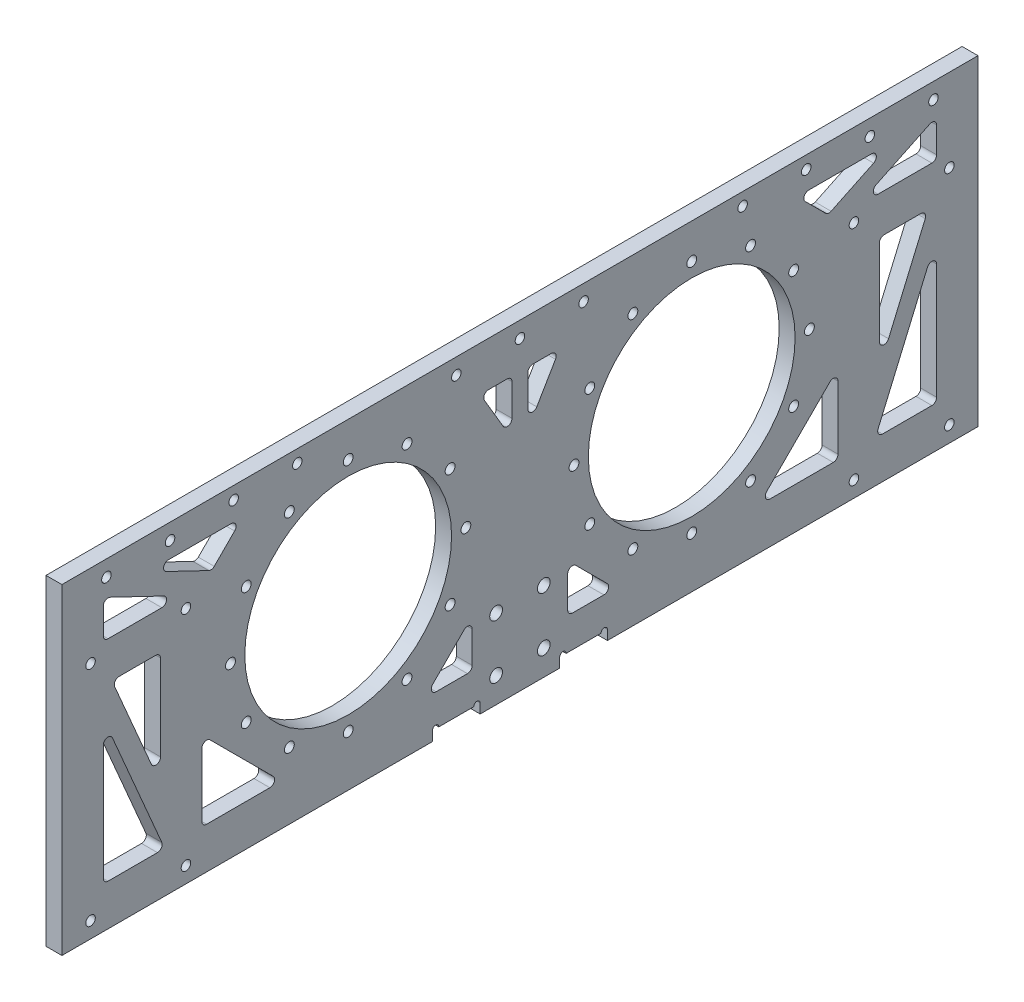
SolidWorks part; units mm, degrees
material "Thornel Mat VMA"
ref_plane "前视基准面" through (0, 0, 0) normal (0, 0, 1) x (1, 0, 0)
ref_plane "上视基准面" through (0, 0, 0) normal (0, 1, 0) x (1, 0, 0)
ref_plane "右视基准面" through (0, 0, 0) normal (1, 0, 0) x (0, 0, -1)
sketch "草图1" plane through (0, 0, 0) normal (1, 0, 0) x (0, 0, -1)
  line L0 (54, 48) -> (54, -53) construction
  line L1 (-90, -53) -> (198, -53)
  line L2 (-90, -53) -> (-90, 48)
  line L3 (-90, 48) -> (198, 48)
  line L4 (198, -53) -> (198, 48)
  line L5 (-36, 44) -> (-16, 44) construction
  line L6 (46.5, -45) -> (61.5, -45) construction
  line L7 (46.5, -45) -> (46.5, -28) construction
  line L8 (46.5, -28) -> (61.5, -28) construction
  line L9 (61.5, -45) -> (61.5, -28) construction
  line L10 (46.5, -45) -> (61.5, -28) construction
  line L11 (46.5, -28) -> (61.5, -45) construction
  line L12 (144, 44) -> (124, 44) construction
  circle A0 centre (0, 0) radius 32.5
  circle A1 centre (0, 0) radius 37 construction
  circle A2 centre (0, 37) radius 1.55
  circle A3 centre (18.5, 32.0429) radius 1.55
  circle A4 centre (32.0429, 18.5) radius 1.55
  circle A5 centre (37, 0) radius 1.55
  circle A6 centre (32.0429, -18.5) radius 1.55
  circle A7 centre (18.5, -32.0429) radius 1.55
  circle A8 centre (0, -37) radius 1.55
  circle A9 centre (-18.5, -32.0429) radius 1.55
  circle A10 centre (-32.0429, -18.5) radius 1.55
  circle A11 centre (-37, 0) radius 1.55
  circle A12 centre (-32.0429, 18.5) radius 1.55
  circle A13 centre (-18.5, 32.0429) radius 1.55
  circle A14 centre (126.5, 32.0429) radius 1.55
  circle A15 centre (140.0429, 18.5) radius 1.55
  circle A16 centre (145, 0) radius 1.55
  circle A17 centre (140.0429, -18.5) radius 1.55
  circle A18 centre (126.5, -32.0429) radius 1.55
  circle A19 centre (108, -37) radius 1.55
  circle A20 centre (89.5, -32.0429) radius 1.55
  circle A21 centre (75.9571, -18.5) radius 1.55
  circle A22 centre (71, 0) radius 1.55
  circle A23 centre (75.9571, 18.5) radius 1.55
  circle A24 centre (89.5, 32.0429) radius 1.55
  circle A25 centre (108, 37) radius 1.55
  circle A26 centre (108, 0) radius 37 construction
  circle A27 centre (108, 0) radius 32.5
  circle A28 centre (0, 0) radius 46 construction
  circle A29 centre (108, 0) radius 46 construction
  circle A30 centre (61.5, -28) radius 2
  circle A31 centre (46.5, -28) radius 2
  circle A32 centre (46.5, -45) radius 2
  circle A33 centre (61.5, -45) radius 2
  circle A34 centre (-16, 44) radius 1.5
  circle A35 centre (-36, 44) radius 1.5
  circle A36 centre (124, 44) radius 1.5
  circle A37 centre (144, 44) radius 1.5
  point P63 (54, -36.5)
  dimension "D1" = 65
  dimension "D2" = 74
  dimension "D4" = 3.1
  dimension "D9" = 92
  dimension "D13" = 4
  dimension "D17" = 3
  dimension "D5" = 53
  dimension "D6" = 48
  dimension "D7" = 90
  dimension "D8" = 108
  dimension "D10" = 25
  dimension "D11" = 17
  dimension "D12" = 15
  dimension "D14" = 70
  dimension "D15" = 20
  dimension "D16" = 4
  dimension "D3" = 12
extrude "凸台-拉伸1" add sketch "草图1" along normal blind 5
sketch "草图2" plane through (5, 0, 0) normal (1, 0, 0) x (0, 0, -1)
  line L0 (-76, 43) -> (-56, 43) construction
  line L1 (54, 48) -> (54, -53) construction
  line L2 (198, 48) -> (-90, 48) construction
  line L3 (-90, -53) -> (198, -53) construction
  line L4 (184, 43) -> (164, 43) construction
  line L5 (-90, 48) -> (-90, -53) construction
  line L6 (34, 43) -> (54, 43) construction
  circle A0 centre (-76, 43) radius 1.5
  circle A1 centre (-56, 43) radius 1.5
  circle A2 centre (164, 43) radius 1.5
  circle A3 centre (184, 43) radius 1.5
  circle A4 centre (34, 43) radius 1.5
  circle A5 centre (54, 43) radius 1.5
  circle A6 centre (74, 43) radius 1.5
  dimension "D1" = 14
  dimension "D4" = 3
  dimension "D6" = 3
  dimension "D2" = 20
  dimension "D3" = 5
  dimension "D5" = 20
extrude "切除-拉伸1" cut sketch "草图2" against normal through all
sketch "草图3" plane through (5, 0, 0) normal (1, 0, 0) x (0, 0, -1)
  line L0 (-81, -48) -> (-51, -48) construction
  line L1 (-90, 48) -> (-90, -53) construction
  line L2 (-90, -53) -> (198, -53) construction
  line L3 (54, 48) -> (54, -53) construction
  line L4 (198, 48) -> (-90, 48) construction
  line L5 (-81, -48) -> (-81, 22) construction
  line L6 (-81, 22) -> (-51, 22) construction
  line L7 (-51, 22) -> (-51, -48) construction
  line L8 (159, 22) -> (159, -48) construction
  line L9 (189, 22) -> (159, 22) construction
  line L10 (189, -48) -> (189, 22) construction
  line L11 (189, -48) -> (159, -48) construction
  circle A0 centre (-81, -48) radius 1.5
  circle A1 centre (-51, -48) radius 1.5
  circle A2 centre (-81, 22) radius 1.5
  circle A3 centre (-51, 22) radius 1.5
  circle A4 centre (159, 22) radius 1.5
  circle A5 centre (189, 22) radius 1.5
  circle A6 centre (159, -48) radius 1.5
  circle A7 centre (189, -48) radius 1.5
  dimension "D3" = 3
  dimension "D1" = 9
  dimension "D2" = 5
  dimension "D4" = 30
  dimension "D5" = 70
extrude "切除-拉伸2" cut sketch "草图3" against normal blind 10
sketch "草图4" plane through (5, 0, 0) normal (1, 0, 0) x (0, 0, -1)
  line L0 (44.1226, 34) -> (50, 34)
  line L1 (51.5, 32.5) -> (51.5, 22.5085)
  line L2 (48.7071, 21.7479) -> (42.8297, 31.7395)
  line L3 (54, 48) -> (54, -53) construction
  line L4 (198, 48) -> (-90, 48) construction
  line L5 (-90, -53) -> (198, -53) construction
  line L6 (56.5, 32.5) -> (56.5, 22.5085)
  line L7 (63.8774, 34) -> (58, 34)
  line L8 (59.2929, 21.7479) -> (65.1703, 31.7395)
  line L9 (-77, -2.257) -> (-77, -38.5)
  line L10 (-81, 22) -> (-51, 22) construction
  line L11 (-81, 22) -> (-81, -48) construction
  line L12 (-81, -48) -> (-51, -48) construction
  line L13 (-51, 22) -> (-51, -48) construction
  line L14 (-75.5, -40) -> (-59.9673, -40)
  line L15 (-58.5886, -37.9091) -> (-74.1213, -1.6661)
  line L16 (-72.0327, 14) -> (-60.5, 14)
  line L17 (-59, 12.5) -> (-59, -14.4097)
  line L18 (-61.8787, -15.0006) -> (-73.4114, 11.9091)
  line L19 (-46, -18.6213) -> (-46, -38.5)
  line L20 (-44.5, -40) -> (-24.6213, -40)
  line L21 (-23.5607, -37.4393) -> (-43.4393, -17.5607)
  line L22 (-77, 35.6161) -> (-77, 27.5)
  line L23 (-75.5, 26) -> (-58.5914, 26)
  line L24 (-57.9423, 28.8523) -> (-74.8509, 36.9684)
  line L25 (-56.5432, 38) -> (-36.7559, 38)
  line L26 (-35.6952, 35.4393) -> (-42.1127, 29.0218)
  line L27 (-43.8225, 28.7302) -> (-57.1923, 35.1477)
  line L34 (27.6213, -40) -> (37.5, -40)
  line L35 (39, -38.5) -> (39, -28.6213)
  line L36 (36.4393, -27.5607) -> (26.5607, -37.4393)
  line L37 (71.5607, -27.5607) -> (81.4393, -37.4393)
  line L38 (69, -38.5) -> (69, -28.6213)
  line L39 (80.3787, -40) -> (70.5, -40)
  line L40 (159, 22) -> (159, -48) construction
  line L41 (189, -48) -> (159, -48) construction
  line L42 (189, 22) -> (189, -48) construction
  line L43 (189, 22) -> (159, 22) construction
  line L50 (151.8225, 28.7302) -> (165.1923, 35.1477)
  line L51 (143.6952, 35.4393) -> (150.1127, 29.0218)
  line L52 (164.5432, 38) -> (144.7559, 38)
  line L53 (165.9423, 28.8523) -> (182.8509, 36.9684)
  line L54 (183.5, 26) -> (166.5914, 26)
  line L55 (185, 35.6161) -> (185, 27.5)
  line L56 (131.5607, -37.4393) -> (151.4393, -17.5607)
  line L57 (152.5, -40) -> (132.6213, -40)
  line L58 (154, -18.6213) -> (154, -38.5)
  line L59 (169.8787, -15.0006) -> (181.4114, 11.9091)
  line L60 (167, 12.5) -> (167, -14.4097)
  line L61 (180.0327, 14) -> (168.5, 14)
  line L62 (166.5886, -37.9091) -> (182.1213, -1.6661)
  line L63 (183.5, -40) -> (167.9673, -40)
  line L64 (185, -2.257) -> (185, -38.5)
  arc A0 (51.5, 22.5085) -> (48.7071, 21.7479) centre (50, 22.5085) cw
  arc A1 (50, 34) -> (51.5, 32.5) centre (50, 32.5) cw
  arc A2 (44.1226, 34) -> (42.8297, 31.7395) centre (44.1226, 32.5) ccw
  arc A3 (58, 34) -> (56.5, 32.5) centre (58, 32.5) ccw
  arc A4 (56.5, 22.5085) -> (59.2929, 21.7479) centre (58, 22.5085) ccw
  arc A5 (63.8774, 34) -> (65.1703, 31.7395) centre (63.8774, 32.5) cw
  arc A7 (-77, -38.5) -> (-75.5, -40) centre (-75.5, -38.5) ccw
  arc A8 (-59.9673, -40) -> (-58.5886, -37.9091) centre (-59.9673, -38.5) ccw
  arc A9 (-77, -2.257) -> (-74.1213, -1.6661) centre (-75.5, -2.257) cw
  arc A10 (-59, -14.4097) -> (-61.8787, -15.0006) centre (-60.5, -14.4097) cw
  arc A11 (-60.5, 14) -> (-59, 12.5) centre (-60.5, 12.5) cw
  arc A12 (-72.0327, 14) -> (-73.4114, 11.9091) centre (-72.0327, 12.5) ccw
  arc A14 (-24.6213, -40) -> (-23.5607, -37.4393) centre (-24.6213, -38.5) ccw
  arc A15 (-46, -38.5) -> (-44.5, -40) centre (-44.5, -38.5) ccw
  arc A16 (-46, -18.6213) -> (-43.4393, -17.5607) centre (-44.5, -18.6213) cw
  arc A23 (-36.7559, 38) -> (-35.6952, 35.4393) centre (-36.7559, 36.5) cw
  arc A24 (-42.1127, 29.0218) -> (-43.8225, 28.7302) centre (-43.1734, 30.0825) cw
  arc A25 (-56.5432, 38) -> (-57.1923, 35.1477) centre (-56.5432, 36.5) ccw
  arc A26 (-58.5914, 26) -> (-57.9423, 28.8523) centre (-58.5914, 27.5) ccw
  arc A27 (-77, 27.5) -> (-75.5, 26) centre (-75.5, 27.5) ccw
  arc A28 (-77, 35.6161) -> (-74.8509, 36.9684) centre (-75.5, 35.6161) cw
  arc A29 (27.6213, -40) -> (26.5607, -37.4393) centre (27.6213, -38.5) cw
  arc A30 (37.5, -40) -> (39, -38.5) centre (37.5, -38.5) ccw
  arc A31 (39, -28.6213) -> (36.4393, -27.5607) centre (37.5, -28.6213) ccw
  arc A32 (69, -28.6213) -> (71.5607, -27.5607) centre (70.5, -28.6213) cw
  arc A33 (70.5, -40) -> (69, -38.5) centre (70.5, -38.5) cw
  arc A34 (80.3787, -40) -> (81.4393, -37.4393) centre (80.3787, -38.5) ccw
  arc A35 (185, 35.6161) -> (182.8509, 36.9684) centre (183.5, 35.6161) ccw
  arc A36 (185, 27.5) -> (183.5, 26) centre (183.5, 27.5) cw
  arc A37 (166.5914, 26) -> (165.9423, 28.8523) centre (166.5914, 27.5) cw
  arc A38 (164.5432, 38) -> (165.1923, 35.1477) centre (164.5432, 36.5) cw
  arc A39 (150.1127, 29.0218) -> (151.8225, 28.7302) centre (151.1734, 30.0825) ccw
  arc A40 (144.7559, 38) -> (143.6952, 35.4393) centre (144.7559, 36.5) ccw
  arc A47 (154, -18.6213) -> (151.4393, -17.5607) centre (152.5, -18.6213) ccw
  arc A48 (154, -38.5) -> (152.5, -40) centre (152.5, -38.5) cw
  arc A49 (132.6213, -40) -> (131.5607, -37.4393) centre (132.6213, -38.5) cw
  arc A50 (180.0327, 14) -> (181.4114, 11.9091) centre (180.0327, 12.5) cw
  arc A51 (168.5, 14) -> (167, 12.5) centre (168.5, 12.5) ccw
  arc A52 (167, -14.4097) -> (169.8787, -15.0006) centre (168.5, -14.4097) ccw
  arc A53 (185, -2.257) -> (182.1213, -1.6661) centre (183.5, -2.257) ccw
  arc A54 (167.9673, -40) -> (166.5886, -37.9091) centre (167.9673, -38.5) cw
  arc A55 (185, -38.5) -> (183.5, -40) centre (183.5, -38.5) cw
  point P11 (51.5, 17)
  point P14 (51.5, 34)
  point P17 (41.5, 34)
  point P73 (-21, -40)
  point P76 (-46, -40)
  point P79 (-46, -15)
  point P97 (-33.1346, 38)
  point P102 (-63.1346, 38)
  point P105 (-52, 26)
  point P108 (-77, 26)
  point P111 (-77, 38)
  point P115 (24, -40)
  point P118 (39, -40)
  point P130 (69, -40)
  point P131 (84, -40)
  point P199 (185, 38)
  point P200 (185, 26)
  point P201 (160, 26)
  point P202 (171.1346, 38)
  point P203 (141.1346, 38)
  point P207 (154, -15)
  point P208 (154, -40)
  point P209 (129, -40)
  dimension "D5" = 1.5
  dimension "D13" = 1.5
  dimension "D26" = 1.5
  dimension "D30" = 1.5
  dimension "D23" = 1.5
  dimension "D1" = 2.5
  dimension "D2" = 14
  dimension "D3" = 10
  dimension "D4" = 17
  dimension "D6" = 8
  dimension "D7" = 4
  dimension "D8" = 8
  dimension "D9" = 16
  dimension "D10" = 3
  dimension "D11" = 3
  dimension "D12" = 3
  dimension "D14" = 5
  dimension "D15" = 25
  dimension "D16" = 25
  dimension "D17" = 10
  dimension "D18" = 4
  dimension "D19" = 25
  dimension "D20" = 6
  dimension "D21" = 45
  dimension "D22" = 30
  dimension "D27" = 15
  dimension "D28" = 45
  dimension "D29" = 15
extrude "切除-拉伸3" cut sketch "草图4" against normal through all
sketch "草图6" plane through (5, 0, 0) normal (1, 0, 0) x (0, 0, -1)
  line L0 (41.5, -53) -> (41.5, -50)
  line L1 (-90, -53) -> (198, -53) construction
  line L5 (54, 48) -> (54, -53) construction
  line L6 (198, 48) -> (-90, 48) construction
  line L7 (39.5, -50) -> (28.5, -50)
  line L8 (26.5, -50) -> (26.5, -53)
  line L9 (26.5, -53) -> (41.5, -53)
  line L13 (81.5, -53) -> (66.5, -53)
  line L14 (81.5, -50) -> (81.5, -53)
  line L15 (68.5, -50) -> (79.5, -50)
  line L16 (66.5, -53) -> (66.5, -50)
  arc A0 (26.5, -50) -> (28.5, -50) centre (27.5, -50) cw
  arc A1 (41.5, -50) -> (39.5, -50) centre (40.5, -50) ccw
  arc A2 (66.5, -50) -> (68.5, -50) centre (67.5, -50) cw
  arc A3 (81.5, -50) -> (79.5, -50) centre (80.5, -50) ccw
  dimension "D4" = 1
  dimension "D1" = 25
  dimension "D2" = 3
  dimension "D3" = 15
extrude "切除-拉伸4" cut sketch "草图6" against normal through all
